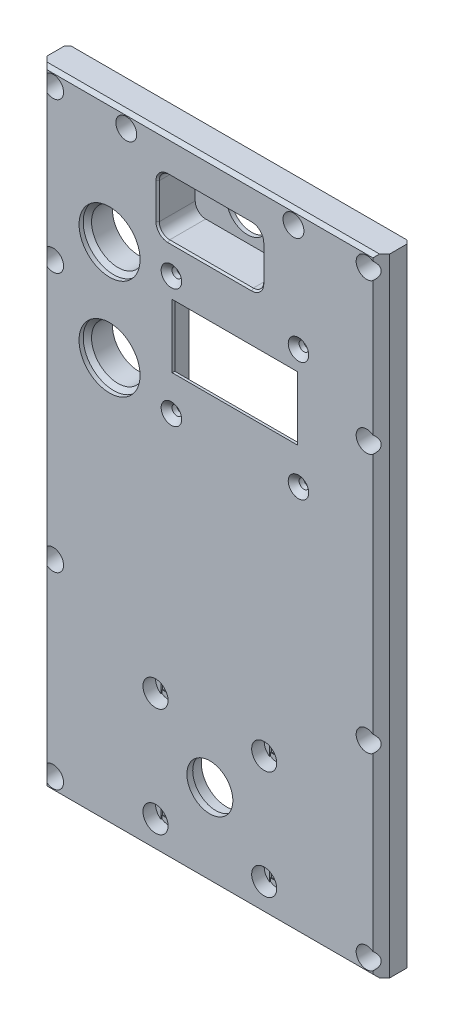
SolidWorks part; units mm, degrees
ref_plane "Front Plane" through (0, 0, 0) normal (0, 0, 1) x (1, 0, 0)
ref_plane "Top Plane" through (0, 0, 0) normal (0, 1, 0) x (1, 0, 0)
ref_plane "Right Plane" through (0, 0, 0) normal (1, 0, 0) x (0, 0, -1)
sketch "Sketch1" plane through (0, 0, 0) normal (0, 0, 1) x (1, 0, 0)
  line L1 (-41, -75) -> (41, -75)
  line L2 (-41, -75) -> (-41, 75)
  line L3 (-41, 75) -> (41, 75)
  line L4 (41, -75) -> (41, 75)
  line L5 (-41, -75) -> (41, 75) construction
  line L6 (-41, 75) -> (41, -75) construction
  line L7 (-34, -68) -> (34, -68)
  line L8 (-34, -68) -> (-34, 68)
  line L9 (-34, 68) -> (34, 68)
  line L10 (34, -68) -> (34, 68)
  line L11 (-34, -68) -> (34, 68) construction
  line L12 (-34, 68) -> (34, -68) construction
  point P0 (0, 0)
  point P6 (0, 0)
  dimension "D1" = 150
  dimension "D2" = 82
  dimension "D3" = 7
  dimension "D4" = 7
extrude "Boss-Extrude1" add sketch "Sketch1" along normal blind 7
sketch "Sketch2" plane through (0, 0, 7) normal (0, 0, 1) x (1, 0, 0)
  line L0 (34, -68) -> (34, 68) construction
  line L1 (-34, -68) -> (34, -68)
  line L2 (-34, -68) -> (-34, -32)
  line L3 (-34, -32) -> (34, -32)
  line L4 (34, -68) -> (34, -32)
  dimension "D1" = 36
extrude "Boss-Extrude2" add sketch "Sketch2" against normal up to surface (7 mm away) up to face at (0, 0, 0)
sketch "Sketch3" plane through (0, 0, 0) normal (0, 0, -1) x (-1, 0, 0)
  line L0 (0, -75) -> (0, -55) construction
  line L1 (41, -75) -> (-41, -75) construction
  circle A0 centre (0, -55) radius 5.5
  dimension "D1" = 11
  dimension "D2" = 20
extrude "Cut-Extrude1" cut sketch "Sketch3" against normal through all
sketch "Sketch4" plane through (0, 0, 0) normal (0, 0, -1) x (-1, 0, 0)
  circle A0 centre (0, -55) radius 6.05
  dimension "D1" = 12.1
extrude "Cut-Extrude2" cut sketch "Sketch4" against normal offset from surface (5.6 mm away) 1.4 up to face at (-5.5, -55, 7)
sketch "Sketch5" plane through (0, 0, 0) normal (0, 0, -1) x (-1, 0, 0)
  circle A0 centre (0, -55) radius 11.1
  dimension "D1" = 22.2
extrude "Cut-Extrude3" cut sketch "Sketch5" against normal offset from surface (3 mm away) 2.6 up to face at (-6.05, -55, 5.6)
sketch "Sketch6" plane through (0, 0, 0) normal (0, 0, -1) x (-1, 0, 0)
  line L1 (-13, -68) -> (13, -68) construction
  line L2 (-13, -68) -> (-13, -42) construction
  line L3 (-13, -42) -> (13, -42) construction
  line L4 (13, -68) -> (13, -42) construction
  line L5 (-13, -68) -> (13, -42) construction
  line L6 (-13, -42) -> (13, -68) construction
  circle A0 centre (-13, -42) radius 1.7
  circle A1 centre (13, -42) radius 1.7
  circle A2 centre (13, -68) radius 1.7
  circle A3 centre (-13, -68) radius 1.7
  point P0 (0, -55)
  dimension "D2" = 3.4
  dimension "D1" = 26
extrude "Cut-Extrude4" cut sketch "Sketch6" against normal through all
sketch "Sketch7" plane through (0, 0, 0) normal (0, 0, -1) x (-1, 0, 0)
  line L1 (-25, -74) -> (25, -74)
  line L2 (-25, -74) -> (-25, -36)
  line L3 (-25, -36) -> (25, -36)
  line L4 (25, -74) -> (25, -36)
  line L5 (-25, -74) -> (25, -36) construction
  line L6 (-25, -36) -> (25, -74) construction
  point P0 (0, -55)
  dimension "D1" = 50
  dimension "D2" = 38
extrude "Cut-Extrude5" cut sketch "Sketch7" against normal blind 1
sketch "Sketch8" plane through (0, 0, 7) normal (0, 0, 1) x (1, 0, 0)
  circle A0 centre (-13, -42) radius 3
  circle A1 centre (13, -42) radius 3
  circle A2 centre (13, -68) radius 3
  circle A3 centre (-13, -68) radius 3
  dimension "D1" = 6
extrude "Cut-Extrude6" cut sketch "Sketch8" against normal blind 3
sketch "Sketch9" plane through (0, 0, 7) normal (0, 0, 1) x (1, 0, 0)
  line L0 (-41, 75) -> (-41, -75) construction
  line L1 (-37.5, -71.5) -> (37.5, -71.5) construction
  line L2 (-37.5, -71.5) -> (-37.5, 71.5) construction
  line L3 (-37.5, 71.5) -> (37.5, 71.5) construction
  line L4 (37.5, -71.5) -> (37.5, 71.5) construction
  line L5 (-37.5, -71.5) -> (37.5, 71.5) construction
  line L6 (-37.5, 71.5) -> (37.5, -71.5) construction
  line L7 (41, 75) -> (-41, 75) construction
  circle A0 centre (-37.5, 71.5) radius 1.45
  circle A1 centre (37.5, 71.5) radius 1.45
  circle A2 centre (37.5, -71.5) radius 1.45
  circle A3 centre (-37.5, -71.5) radius 1.45
  circle A6 centre (-37.5, 35.5) radius 1.45
  circle A7 centre (-37.5, -26.5) radius 1.45
  circle A8 centre (37.5, -26.5) radius 1.45
  circle A9 centre (37.5, 35.5) radius 1.45
  point P0 (0, 0)
  dimension "D3" = 2.9
  dimension "D4" = 45
  dimension "D5" = 36
  dimension "D1" = 3.5
  dimension "D2" = 3.5
extrude "Cut-Extrude7" cut sketch "Sketch9" against normal through all
sketch "Sketch10" plane through (0, 0, 7) normal (0, 0, 1) x (1, 0, 0)
  circle A0 centre (-37.5, 71.5) radius 2.5
  circle A1 centre (37.5, 71.5) radius 2.5
  circle A2 centre (-37.5, 35.5) radius 2.5
  circle A3 centre (-37.5, -26.5) radius 2.5
  circle A4 centre (-37.5, -71.5) radius 2.5
  circle A5 centre (37.5, -71.5) radius 2.5
  circle A6 centre (37.5, 35.5) radius 2.5
  circle A7 centre (37.5, -26.5) radius 2.5
  dimension "D1" = 5
extrude "Cut-Extrude8" cut sketch "Sketch10" against normal blind 5
chamfer "Chamfer1" distance 2 angle 45 2 edges at (-41, 0, 7) (41, 0, 7)
sketch "Sketch11" plane through (0, 0, 7) normal (0, 0, 1) x (1, 0, 0)
  line L0 (34, -32) -> (34, 68) construction
  line L1 (-34, -32) -> (34, -32)
  line L2 (-34, -32) -> (-34, -1.5)
  line L3 (-34, -1.5) -> (34, -1.5)
  line L4 (34, -32) -> (34, -1.5)
  line L5 (-39, -75) -> (39, -75) construction
  dimension "D1" = 73.5
extrude "Boss-Extrude3" add sketch "Sketch11" against normal up to surface (7 mm away) up to face at (38.95, 71.5, 0)
sketch "Sketch12" plane through (0, 0, 2) normal (0, 0, 1) x (1, 0, 0)
  line L2 (-38.95, -73.5365) -> (-38.95, -69.4635)
  line L4 (-36.05, -73.5365) -> (-36.05, -69.4635)
  line L5 (-38.95, -73.5365) -> (-36.05, -69.4635) construction
  line L6 (-38.95, -69.4635) -> (-36.05, -73.5365) construction
  line L8 (-38.95, -28.5365) -> (-38.95, -24.4635)
  line L10 (-36.05, -28.5365) -> (-36.05, -24.4635)
  line L11 (-38.95, -28.5365) -> (-36.05, -24.4635) construction
  line L12 (-38.95, -24.4635) -> (-36.05, -28.5365) construction
  line L14 (-38.95, 33.4635) -> (-38.95, 37.5365)
  line L16 (-36.05, 33.4635) -> (-36.05, 37.5365)
  line L17 (-38.95, 33.4635) -> (-36.05, 37.5365) construction
  line L18 (-38.95, 37.5365) -> (-36.05, 33.4635) construction
  line L20 (-38.95, 69.4635) -> (-38.95, 73.5365)
  line L22 (-36.05, 69.4635) -> (-36.05, 73.5365)
  line L23 (-38.95, 69.4635) -> (-36.05, 73.5365) construction
  line L24 (-38.95, 73.5365) -> (-36.05, 69.4635) construction
  arc A0 (-39, -73.5) -> (-39, -69.5) centre (-37.5, -71.5) ccw construction
  circle A1 centre (-37.5, -26.5) radius 2.5 construction
  circle A2 centre (-37.5, 35.5) radius 2.5 construction
  arc A3 (-39, 69.5) -> (-39, 73.5) centre (-37.5, 71.5) ccw construction
  circle A4 centre (-37.5, 71.5) radius 1.45 construction
  circle A5 centre (-37.5, 71.5) radius 2.5 construction
  arc A6 (-36.05, 73.5365) -> (-38.95, 73.5365) centre (-37.5, 71.5) ccw
  arc A7 (-38.95, 69.4635) -> (-36.05, 69.4635) centre (-37.5, 71.5) ccw
  circle A8 centre (-37.5, 35.5) radius 1.45 construction
  arc A9 (-38.95, 33.4635) -> (-36.05, 33.4635) centre (-37.5, 35.5) ccw
  arc A10 (-36.05, 37.5365) -> (-38.95, 37.5365) centre (-37.5, 35.5) ccw
  circle A11 centre (-37.5, -26.5) radius 1.45 construction
  arc A12 (-38.95, -28.5365) -> (-36.05, -28.5365) centre (-37.5, -26.5) ccw
  arc A13 (-36.05, -24.4635) -> (-38.95, -24.4635) centre (-37.5, -26.5) ccw
  circle A14 centre (-37.5, -71.5) radius 1.45 construction
  arc A16 (-38.95, -73.5365) -> (-36.05, -73.5365) centre (-37.5, -71.5) ccw
  arc A18 (-36.05, -69.4635) -> (-38.95, -69.4635) centre (-37.5, -71.5) ccw
  point P0 (-37.5, -71.5)
  point P9 (-37.5, -26.5)
  point P17 (-37.5, 35.5)
  point P25 (-37.5, 71.5)
extrude "Cut-Extrude9" cut sketch "Sketch12" against normal blind 0.2
sketch "Sketch13" plane through (0, 0, 1.8) normal (0, 0, 1) x (1, 0, 0)
  line L0 (-36.05, -71.5) -> (-36.05, -69.4635) construction
  line L1 (-38.95, -72.95) -> (-36.05, -72.95)
  line L2 (-38.95, -72.95) -> (-38.95, -70.05)
  line L3 (-38.95, -70.05) -> (-36.05, -70.05)
  line L4 (-36.05, -72.95) -> (-36.05, -70.05)
  line L5 (-38.95, -72.95) -> (-36.05, -70.05) construction
  line L6 (-38.95, -70.05) -> (-36.05, -72.95) construction
  line L7 (-36.05, -26.5) -> (-36.05, -24.4635) construction
  line L8 (-38.95, -27.95) -> (-36.05, -27.95)
  line L9 (-38.95, -27.95) -> (-38.95, -25.05)
  line L10 (-38.95, -25.05) -> (-36.05, -25.05)
  line L11 (-36.05, -27.95) -> (-36.05, -25.05)
  line L12 (-38.95, -27.95) -> (-36.05, -25.05) construction
  line L13 (-38.95, -25.05) -> (-36.05, -27.95) construction
  line L14 (-36.05, 33.4635) -> (-36.05, 37.5365) construction
  line L15 (-38.95, 34.05) -> (-36.05, 34.05)
  line L16 (-38.95, 34.05) -> (-38.95, 36.95)
  line L17 (-38.95, 36.95) -> (-36.05, 36.95)
  line L18 (-36.05, 34.05) -> (-36.05, 36.95)
  line L19 (-38.95, 34.05) -> (-36.05, 36.95) construction
  line L20 (-38.95, 36.95) -> (-36.05, 34.05) construction
  line L21 (-36.05, 69.4635) -> (-36.05, 73.5365) construction
  line L22 (-38.95, 70.05) -> (-36.05, 70.05)
  line L23 (-38.95, 70.05) -> (-38.95, 72.95)
  line L24 (-38.95, 72.95) -> (-36.05, 72.95)
  line L25 (-36.05, 70.05) -> (-36.05, 72.95)
  line L26 (-38.95, 70.05) -> (-36.05, 72.95) construction
  line L27 (-38.95, 72.95) -> (-36.05, 70.05) construction
  arc A0 (-36.05, -71.5) -> (-38.95, -71.5) centre (-37.5, -71.5) ccw construction
  arc A1 (-36.05, -26.5) -> (-38.95, -26.5) centre (-37.5, -26.5) ccw construction
  arc A2 (-36.05, 35.5) -> (-38.95, 35.5) centre (-37.5, 35.5) ccw construction
  arc A3 (-36.05, 71.5) -> (-38.95, 71.5) centre (-37.5, 71.5) ccw construction
  point P0 (-37.5, -71.5)
  point P11 (-37.5, -26.5)
  point P22 (-37.5, 35.5)
  point P33 (-37.5, 71.5)
extrude "Cut-Extrude10" cut sketch "Sketch13" against normal blind 0.2
sketch "Sketch14" plane through (0, 0, 4) normal (0, 0, 1) x (1, 0, 0)
  line L2 (-14.7, -44.4718) -> (-14.7, -39.5282)
  line L4 (-11.3, -44.4718) -> (-11.3, -39.5282)
  line L5 (-14.7, -44.4718) -> (-11.3, -39.5282) construction
  line L6 (-14.7, -39.5282) -> (-11.3, -44.4718) construction
  line L8 (-14.7, -70.4718) -> (-14.7, -65.5282)
  line L10 (-11.3, -70.4718) -> (-11.3, -65.5282)
  line L11 (-14.7, -70.4718) -> (-11.3, -65.5282) construction
  line L12 (-14.7, -65.5282) -> (-11.3, -70.4718) construction
  circle A0 centre (-13, -42) radius 3 construction
  circle A1 centre (-13, -68) radius 3 construction
  circle A2 centre (-13, -42) radius 3 construction
  arc A3 (-14.7, -44.4718) -> (-11.3, -44.4718) centre (-13, -42) ccw
  arc A4 (-14.7, -70.4718) -> (-11.3, -70.4718) centre (-13, -68) ccw
  circle A5 centre (-13, -42) radius 1.7 construction
  circle A6 centre (-13, -68) radius 1.7 construction
  arc A7 (-11.3, -39.5282) -> (-14.7, -39.5282) centre (-13, -42) ccw
  arc A8 (-11.3, -65.5282) -> (-14.7, -65.5282) centre (-13, -68) ccw
  point P0 (-13, -42)
  point P8 (-13, -68)
extrude "Cut-Extrude11" cut sketch "Sketch14" against normal blind 0.2
sketch "Sketch15" plane through (0, 0, 3.8) normal (0, 0, 1) x (1, 0, 0)
  line L0 (-11.3, -42) -> (-11.3, -39.5282) construction
  line L1 (-14.7, -43.7) -> (-11.3, -43.7)
  line L2 (-14.7, -43.7) -> (-14.7, -40.3)
  line L3 (-14.7, -40.3) -> (-11.3, -40.3)
  line L4 (-11.3, -43.7) -> (-11.3, -40.3)
  line L5 (-14.7, -43.7) -> (-11.3, -40.3) construction
  line L6 (-14.7, -40.3) -> (-11.3, -43.7) construction
  line L7 (-11.3, -68) -> (-11.3, -65.5282) construction
  line L8 (-14.7, -69.7) -> (-11.3, -69.7)
  line L9 (-14.7, -69.7) -> (-14.7, -66.3)
  line L10 (-14.7, -66.3) -> (-11.3, -66.3)
  line L11 (-11.3, -69.7) -> (-11.3, -66.3)
  line L12 (-14.7, -69.7) -> (-11.3, -66.3) construction
  line L13 (-14.7, -66.3) -> (-11.3, -69.7) construction
  arc A0 (-11.3, -68) -> (-14.7, -68) centre (-13, -68) ccw construction
  arc A1 (-14.7, -42) -> (-11.3, -42) centre (-13, -42) ccw construction
  point P0 (-13, -42)
  point P8 (-13, -68)
extrude "Cut-Extrude12" cut sketch "Sketch15" against normal blind 0.2
mirror "Mirror1" about plane through (0, 0, 0) normal (1, 0, 0) of "Cut-Extrude10", "Cut-Extrude11", "Cut-Extrude12", "Cut-Extrude9"
chamfer "Chamfer3" distance 0.8 angle 45 4 edges at (-41, 0, 0) (41, 0, 0) (0, -75, 7) (0, 75, 7)
sketch "Sketch16" plane through (0, 0, 0) normal (1, 0, 0) x (0, 0, -1)
  line L0 (0, -4) -> (0, -15.4)
  line L1 (0, 75) -> (0, -75) construction
  line L2 (0, -15.4) -> (3.2, -12.2)
  line L3 (3.2, -12.2) -> (3.2, -7.2)
  line L4 (3.2, -7.2) -> (0, -4)
  line L5 (0, -15.4) -> (0, -19.4) construction
  line L6 (0.6, -7.7) -> (2.6, -7.7)
  line L7 (0.6, -7.7) -> (0.6, -11.7)
  line L8 (0.6, -11.7) -> (2.6, -11.7)
  line L9 (2.6, -7.7) -> (2.6, -11.7)
  line L10 (-1.046, -17.4) -> (12.8392, -17.4) construction
  line L11 (2.6, -27.1) -> (2.6, -23.1)
  line L12 (0.6, -23.1) -> (2.6, -23.1)
  line L13 (0.6, -27.1) -> (0.6, -23.1)
  line L14 (0.6, -27.1) -> (2.6, -27.1)
  line L15 (3.2, -27.6) -> (0, -30.8)
  line L16 (3.2, -22.6) -> (3.2, -27.6)
  line L17 (0, -19.4) -> (3.2, -22.6)
  line L18 (0, -30.8) -> (0, -19.4)
  point P10 (2.6, -9.7)
  point P11 (3.2, -9.7)
  point P24 (0, -17.4)
  dimension "D1" = 5
  dimension "D2" = 2
  dimension "D3" = 0.6
  dimension "D4" = 0.6
  dimension "D5" = 45
  dimension "D6" = 4
  dimension "D7" = 4
  dimension "D8" = 4
extrude "Boss-Extrude4" add sketch "Sketch16" along normal mid plane 2
pattern_linear "LPattern1" count 2 spacing 20 along (1, 0, 0) count 2 spacing 20 along (-1, 0, 0) of "Boss-Extrude4"
sketch "Sketch17" plane through (0, 0, 0) normal (0, 0, -1) x (-1, 0, 0)
  line L0 (-20, 71.5) -> (20, 71.5) construction
  line L1 (-40.2, 75) -> (40.2, 75) construction
  circle A0 centre (-37.5, 71.5) radius 1.45 construction
  circle A1 centre (-37.5, 71.5) radius 1.45 construction
  circle A2 centre (-20, 71.5) radius 1.45
  circle A3 centre (20, 71.5) radius 1.45
  point P3 (0, 71.5)
  point P6 (0, 75)
  dimension "D1" = 40
extrude "Cut-Extrude13" cut sketch "Sketch17" against normal through all
sketch "Sketch18" plane through (0, 0, 7) normal (0, 0, 1) x (1, 0, 0)
  circle A0 centre (-20, 71.5) radius 2.5
  circle A1 centre (20, 71.5) radius 2.5
  arc A2 (-39, 69.5) -> (-39, 73.5) centre (-37.5, 71.5) ccw construction
extrude "Cut-Extrude14" cut sketch "Sketch18" against normal up to surface (5 mm away) up to face at (35.525, 71.5, 2)
sketch "Sketch19" plane through (0, 0, 2) normal (0, 0, 1) x (1, 0, 0)
  line L2 (-21.45, 69.4635) -> (-21.45, 73.5365)
  line L4 (-18.55, 69.4635) -> (-18.55, 73.5365)
  line L5 (-21.45, 69.4635) -> (-18.55, 73.5365) construction
  line L6 (-21.45, 73.5365) -> (-18.55, 69.4635) construction
  line L8 (18.55, 69.4635) -> (18.55, 73.5365)
  line L10 (21.45, 69.4635) -> (21.45, 73.5365)
  line L11 (18.55, 69.4635) -> (21.45, 73.5365) construction
  line L12 (18.55, 73.5365) -> (21.45, 69.4635) construction
  circle A0 centre (-20, 71.5) radius 2.5 construction
  circle A1 centre (20, 71.5) radius 2.5 construction
  circle A2 centre (20, 71.5) radius 1.45 construction
  circle A3 centre (-20, 71.5) radius 1.45 construction
  circle A4 centre (-20, 71.5) radius 2.5 construction
  arc A5 (18.55, 69.4635) -> (21.45, 69.4635) centre (20, 71.5) ccw
  arc A6 (-18.55, 73.5365) -> (-21.45, 73.5365) centre (-20, 71.5) ccw
  arc A7 (21.45, 73.5365) -> (18.55, 73.5365) centre (20, 71.5) ccw
  arc A8 (-21.45, 69.4635) -> (-18.55, 69.4635) centre (-20, 71.5) ccw
  point P0 (-20, 71.5)
  point P8 (20, 71.5)
extrude "Cut-Extrude15" cut sketch "Sketch19" against normal blind 0.2
sketch "Sketch20" plane through (0, 0, 1.8) normal (0, 0, 1) x (1, 0, 0)
  line L0 (-18.55, 69.4635) -> (-18.55, 73.5365) construction
  line L1 (-21.45, 70.05) -> (-18.55, 70.05)
  line L2 (-21.45, 70.05) -> (-21.45, 72.95)
  line L3 (-21.45, 72.95) -> (-18.55, 72.95)
  line L4 (-18.55, 70.05) -> (-18.55, 72.95)
  line L5 (-21.45, 70.05) -> (-18.55, 72.95) construction
  line L6 (-21.45, 72.95) -> (-18.55, 70.05) construction
  line L7 (21.45, 71.5) -> (21.45, 73.5365) construction
  line L8 (18.55, 70.05) -> (21.45, 70.05)
  line L9 (18.55, 70.05) -> (18.55, 72.95)
  line L10 (18.55, 72.95) -> (21.45, 72.95)
  line L11 (21.45, 70.05) -> (21.45, 72.95)
  line L12 (18.55, 70.05) -> (21.45, 72.95) construction
  line L13 (18.55, 72.95) -> (21.45, 70.05) construction
  arc A0 (18.55, 71.5) -> (21.45, 71.5) centre (20, 71.5) ccw construction
  point P0 (-20, 71.5)
  point P8 (20, 71.5)
extrude "Cut-Extrude16" cut sketch "Sketch20" against normal blind 0.2
sketch "Skizze4" plane through (0, 0, 0) normal (0, 0, -1) x (-1, 0, 0)
  line L1 (21, -4) -> (-21, -4)
  line L2 (21, -4) -> (21, -30.8)
  line L3 (21, -30.8) -> (-21, -30.8)
  line L4 (-21, -4) -> (-21, -30.8)
extrude "Schnitt-Linear austragen1" cut sketch "Skizze4" along normal up to surface (3.2 mm away) up to face at (-20, -9.7, -3.2)
sketch "Sketch38" plane through (0, 0, 7) normal (0, 0, 1) x (1, 0, 0)
  line L0 (34, -1.5) -> (34, 68) construction
  line L1 (-34, 68) -> (34, 68)
  line L2 (-34, 68) -> (-34, 12)
  line L3 (-34, 12) -> (34, 12)
  line L4 (34, 68) -> (34, 12)
  dimension "D1" = 56
extrude "Boss-Extrude12" add sketch "Sketch38" against normal up to surface (7 mm away) up to face at (18.55, 71.5, 0)
sketch "Sketch41" plane through (0, 0, 7) normal (0, 0, 1) x (1, 0, 0)
  line L1 (-34, 12) -> (34, 12)
  line L2 (-34, 12) -> (-34, -1.5)
  line L3 (-34, -1.5) -> (34, -1.5)
  line L4 (34, 12) -> (34, -1.5)
extrude "Boss-Extrude13" add sketch "Sketch41" against normal up to surface (7 mm away) up to face at (18.55, 71.5, 0)
sketch "Sketch40" plane through (0, 0, 0) normal (0, 0, -1) x (-1, 0, 0)
  line L0 (-6, 66.6873) -> (-6, -2.4873) construction
  line L1 (-23.8, 15.25) -> (11.8, 15.25) construction
  line L2 (-23.8, 15.25) -> (-23.8, 48.95) construction
  line L3 (-23.8, 48.95) -> (11.8, 48.95) construction
  line L4 (11.8, 15.25) -> (11.8, 48.95) construction
  line L5 (-23.8, 15.25) -> (11.8, 48.95) construction
  line L6 (-23.8, 48.95) -> (11.8, 15.25) construction
  line L7 (-21.2, 17.85) -> (9.2, 17.85) construction
  line L8 (-21.2, 17.85) -> (-21.2, 46.35) construction
  line L9 (-21.2, 46.35) -> (9.2, 46.35) construction
  line L10 (9.2, 17.85) -> (9.2, 46.35) construction
  line L11 (-21.2, 17.85) -> (9.2, 46.35) construction
  line L12 (-21.2, 46.35) -> (9.2, 17.85) construction
  line L13 (-24.05, 15) -> (12.05, 15)
  line L14 (-24.05, 15) -> (-24.05, 49.2)
  line L15 (-24.05, 49.2) -> (12.05, 49.2)
  line L16 (12.05, 15) -> (12.05, 49.2)
  line L17 (-24.05, 15) -> (12.05, 49.2) construction
  line L18 (-24.05, 49.2) -> (12.05, 15) construction
  line L19 (-21, 26.4) -> (9, 26.4) construction
  line L20 (-21, 26.4) -> (-21, 41.6) construction
  line L21 (-21, 41.6) -> (9, 41.6) construction
  line L22 (9, 26.4) -> (9, 41.6) construction
  line L23 (-21, 26.4) -> (9, 41.6) construction
  line L24 (-21, 41.6) -> (9, 26.4) construction
  line L25 (-6, 34) -> (24, 34) construction
  line L26 (24, 22) -> (24, 46) construction
  circle A0 centre (-21.2, 46.35) radius 1.5 construction
  circle A1 centre (9.2, 46.35) radius 1.5 construction
  circle A2 centre (9.2, 17.85) radius 1.5 construction
  circle A3 centre (-21.2, 17.85) radius 1.5 construction
  circle A4 centre (24, 46) radius 6.3
  circle A5 centre (24, 22) radius 6.3
  circle A6 centre (24, 22) radius 7
  circle A7 centre (24, 46) radius 7
  point P2 (-6, 32.1)
  point P7 (-6, 32.1)
  point P16 (-6, 32.1)
  point P21 (-6, 34)
  point P32 (24, 34)
  dimension "D5" = 3
  dimension "D12" = 6
  dimension "D13" = 12.6
  dimension "D14" = 14
  dimension "D1" = 35.6
  dimension "D2" = 33.7
  dimension "D3" = 30.4
  dimension "D4" = 28.5
  dimension "D6" = 0.25
  dimension "D7" = 0.25
  dimension "D8" = 15.2
  dimension "D9" = 30
  dimension "D10" = 7.35
  dimension "D11" = 15
  dimension "D15" = 24
  dimension "D16" = 30
sketch "Sketch42" plane through (0, 0, 0) normal (0, 0, -1) x (-1, 0, 0)
  line L0 (-24.05, 15) -> (12.05, 15) construction
  line L1 (12.05, 15) -> (12.05, 49.2) construction
  line L2 (-24.05, 49.2) -> (12.05, 49.2) construction
  line L3 (-24.05, 15) -> (-24.05, 49.2) construction
  line L4 (-24.05, 15) -> (12.05, 15)
  line L5 (12.05, 15) -> (12.05, 49.2)
  line L6 (-24.05, 49.2) -> (12.05, 49.2)
  line L7 (-24.05, 15) -> (-24.05, 49.2)
extrude "Cut-Extrude17" cut sketch "Sketch42" against normal offset from surface (6.4 mm away) 0.6 up to face at (-17.5, 71.5, 7)
sketch "Sketch43" plane through (0, 0, 6.4) normal (0, 0, -1) x (-1, 0, 0)
  line L0 (-21, 26.4) -> (-21, 41.6) construction
  line L1 (-21, 26.4) -> (9, 26.4) construction
  line L2 (9, 26.4) -> (9, 41.6) construction
  line L3 (-21, 41.6) -> (9, 41.6) construction
  line L4 (-21, 26.4) -> (-21, 41.6)
  line L5 (-21, 26.4) -> (9, 26.4)
  line L6 (9, 26.4) -> (9, 41.6)
  line L7 (-21, 41.6) -> (9, 41.6)
extrude "Cut-Extrude18" cut sketch "Sketch43" against normal through all
sketch "Sketch44" plane through (0, 0, 0) normal (0, 0, -1) x (-1, 0, 0)
  circle A0 centre (24, 22) radius 6.3 construction
  circle A1 centre (24, 46) radius 6.3 construction
  circle A2 centre (24, 22) radius 6.3
  circle A3 centre (24, 46) radius 6.3
extrude "Cut-Extrude19" cut sketch "Sketch44" against normal through all
sketch "Sketch45" plane through (0, 0, 6.4) normal (0, 0, -1) x (-1, 0, 0)
  line L1 (-24.05, 49.2) -> (-19.2, 49.2)
  line L2 (-24.05, 49.2) -> (-24.05, 44.35)
  line L3 (-24.05, 44.35) -> (-19.2, 44.35)
  line L4 (-19.2, 49.2) -> (-19.2, 44.35)
  line L5 (12.05, 49.2) -> (7.2, 49.2)
  line L6 (12.05, 49.2) -> (12.05, 44.35)
  line L7 (12.05, 44.35) -> (7.2, 44.35)
  line L8 (7.2, 49.2) -> (7.2, 44.35)
  line L9 (12.05, 15) -> (7.2, 15)
  line L10 (12.05, 15) -> (12.05, 19.85)
  line L11 (12.05, 19.85) -> (7.2, 19.85)
  line L12 (7.2, 15) -> (7.2, 19.85)
  line L13 (-24.05, 15) -> (-19.2, 15)
  line L14 (-24.05, 15) -> (-24.05, 19.85)
  line L15 (-24.05, 19.85) -> (-19.2, 19.85)
  line L16 (-19.2, 15) -> (-19.2, 19.85)
  circle A0 centre (-21.2, 46.35) radius 1.5 construction
  dimension "D1" = 2
extrude "Boss-Extrude14" add sketch "Sketch45" along normal blind 1.8
sketch "Sketch46" plane through (0, 0, 4.6) normal (0, 0, -1) x (-1, 0, 0)
  circle A0 centre (9.2, 17.85) radius 1.55
  circle A1 centre (-21.2, 17.85) radius 1.55
  circle A2 centre (-21.2, 46.35) radius 1.55
  circle A3 centre (9.2, 46.35) radius 1.55
  dimension "D1" = 3.1
extrude "Boss-Extrude15" add sketch "Sketch46" along normal blind 2
sketch "Sketch47" plane through (0, 0, 0) normal (0, 0, -1) x (-1, 0, 0)
  line L1 (-28.79, 50.463) -> (15.71, 50.463)
  line L2 (-28.79, 50.463) -> (-28.79, 13.463)
  line L3 (-28.79, 13.463) -> (15.71, 13.463)
  line L4 (15.71, 50.463) -> (15.71, 13.463)
  dimension "D1" = 44.5
  dimension "D2" = 37
sketch "Sketch48" plane through (0, 0, 0) normal (0, 0, -1) x (-1, 0, 0)
  line L1 (-17.5, 51.3083) -> (17.5, 51.3083)
  line L2 (-17.5, 51.3083) -> (-17.5, 71.3083)
  line L3 (-17.5, 71.3083) -> (17.5, 71.3083)
  line L4 (17.5, 51.3083) -> (17.5, 71.3083)
  line L5 (-17.5, 51.3083) -> (17.5, 71.3083) construction
  line L6 (-17.5, 71.3083) -> (17.5, 51.3083) construction
  point P0 (0, 61.3083)
  dimension "D1" = 35
  dimension "D2" = 20
sketch "Sketch49" plane through (0, 0, 7) normal (0, 0, 1) x (1, 0, 0)
  line L0 (-39.8, 75) -> (39.8, 75) construction
  line L1 (-12.5, 53.25) -> (12.5, 53.25)
  line L2 (-12.5, 53.25) -> (-12.5, 66.75)
  line L3 (-12.5, 66.75) -> (12.5, 66.75)
  line L4 (12.5, 53.25) -> (12.5, 66.75)
  line L5 (-12.5, 53.25) -> (12.5, 66.75) construction
  line L6 (-12.5, 66.75) -> (12.5, 53.25) construction
  point P0 (0, 60)
  dimension "D1" = 25
  dimension "D2" = 13.5
  dimension "D3" = 15
extrude "Cut-Extrude20" cut sketch "Sketch49" against normal through all
sketch "Sketch50" plane through (0, 0, 0) normal (0, 0, -1) x (-1, 0, 0)
  line L0 (12.5, 66.75) -> (12.5, 53.25) construction
  line L1 (12.5, 53.25) -> (-12.5, 53.25) construction
  line L2 (-12.5, 53.25) -> (-12.5, 66.75) construction
  line L3 (-12.5, 66.75) -> (12.5, 66.75) construction
  line L4 (12.5, 66.75) -> (12.5, 53.25)
  line L5 (12.5, 53.25) -> (-12.5, 53.25)
  line L6 (-12.5, 53.25) -> (-12.5, 66.75)
  line L7 (-12.5, 66.75) -> (12.5, 66.75)
  line L8 (12.5, 66.75) -> (-12.5, 53.25) construction
  line L10 (-14.5, 51.25) -> (14.5, 51.25)
  line L11 (-14.5, 51.25) -> (-14.5, 68.75)
  line L12 (-14.5, 68.75) -> (14.5, 68.75)
  line L13 (14.5, 51.25) -> (14.5, 68.75)
  line L14 (-14.5, 51.25) -> (14.5, 68.75) construction
  line L15 (-14.5, 68.75) -> (14.5, 51.25) construction
  point P2 (0, 60)
  dimension "D1" = 2
  dimension "D2" = 2
extrude "Boss-Extrude16" add sketch "Sketch50" along normal offset from surface (2 mm away) 9 up to face at (0, 60, 7)
sketch "Sketch51" plane through (0, 0, -2) normal (0, 0, -1) x (-1, 0, 0)
  line L4 (-14.5, 51.25) -> (14.5, 51.25)
  line L5 (14.5, 51.25) -> (14.5, 68.75)
  line L6 (14.5, 68.75) -> (-14.5, 68.75)
  line L7 (-14.5, 68.75) -> (-14.5, 51.25)
  line L8 (-14.5, 51.25) -> (14.5, 51.25)
  line L9 (14.5, 51.25) -> (14.5, 68.75)
  line L10 (14.5, 68.75) -> (-14.5, 68.75)
  line L11 (-14.5, 68.75) -> (-14.5, 51.25)
  dimension "D1" = 0
extrude "Boss-Extrude17" add sketch "Sketch51" along normal blind 1
sketch "Sketch52" plane through (0, 0, -3) normal (0, 0, -1) x (-1, 0, 0)
  line L0 (14.5, 68.75) -> (-14.5, 51.25) construction
  circle A0 centre (0, 60) radius 5
  dimension "D1" = 10
extrude "Cut-Extrude21" cut sketch "Sketch52" against normal through all both and the other way through all
sketch "Sketch53" plane through (12.5, 0, 0) normal (-1, 0, 0) x (0, 0, 1)
  line L0 (-2, 66.75) -> (-2, 53.25) construction
  line L1 (-2, 62.5) -> (6.4, 62.5)
  line L2 (-2, 62.5) -> (-2, 57.5)
  line L3 (-2, 57.5) -> (6.4, 57.5)
  line L4 (6.4, 62.5) -> (6.4, 57.5)
  line L5 (7, 53.25) -> (7, 66.75) construction
  point P8 (6.4, 60)
  point P9 (7, 60)
  dimension "D1" = 0.6
  dimension "D2" = 5
extrude "Cut-Extrude22" cut sketch "Sketch53" against normal blind 6
sketch "Sketch54" plane through (0, 0, 7) normal (0, 0, 1) x (1, 0, 0)
  circle A0 centre (-24, 46) radius 7.3
  circle A1 centre (-24, 22) radius 7.3
  dimension "D1" = 14.6
extrude "Cut-Extrude23" cut sketch "Sketch54" against normal blind 1
chamfer "Chamfer4" distance 1 angle 45 2 edges at (-17.7, 22, 6) (-17.7, 46, 6)
fillet "Fillet1" radius 2.5 4 edges at (12.5, 53.25, 2.5) (-12.5, 53.25, 2.5) (12.5, 66.75, 2.5) (-12.5, 66.75, 2.5)
chamfer "Chamfer5" distance 0.4 angle 45 8 edges at (0, 53.25, 7) (11.7678, 53.9822, 7) (-11.7678, 53.9822, 7) (12.5, 60, 7) (-12.5, 60, 7) (11.7678, 66.0178, 7) (-11.7678, 66.0178, 7) (0, 66.75, 7)
sketch "Sketch55" plane through (0, 0, 4.6) normal (0, 0, -1) x (-1, 0, 0)
  circle A0 centre (-21.2, 46.35) radius 1.55
  circle A1 centre (9.2, 46.35) radius 1.55
  circle A2 centre (9.2, 17.85) radius 1.55
  circle A3 centre (-21.2, 17.85) radius 1.55
  circle A4 centre (-21.2, 46.35) radius 1.55 construction
sketch "Sketch56" plane through (0, 0, 4.6) normal (0, 0, -1) x (-1, 0, 0)
  circle A0 centre (-21.2, 46.35) radius 1.15
  circle A1 centre (9.2, 46.35) radius 1.15
  circle A2 centre (9.2, 17.85) radius 1.15
  circle A3 centre (-21.2, 17.85) radius 1.15
  dimension "D1" = 2.3
extrude "Cut-Extrude25" cut sketch "Sketch56" against normal through all
extrude "Cut-Extrude26" cut sketch "Sketch55" along normal through all
chamfer "Chamfer6" distance 1.3 angle 45 4 edges at (-10.35, 46.35, 7) (-10.35, 17.85, 7) (20.05, 17.85, 7) (20.05, 46.35, 7)
